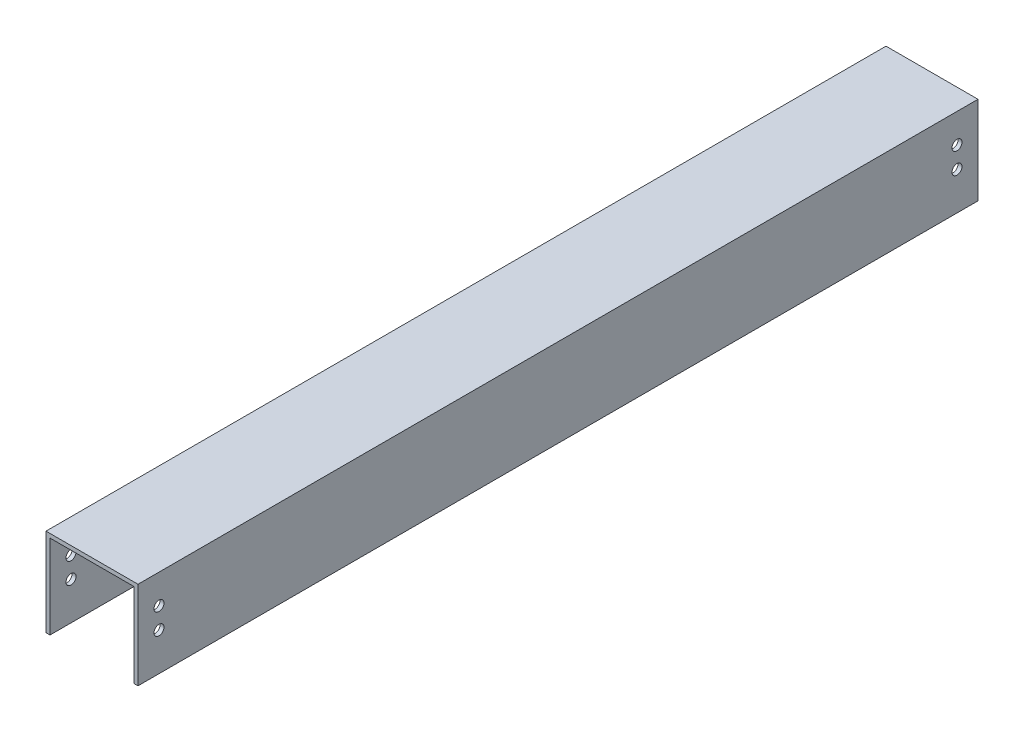
SolidWorks part; units mm, degrees
material "AISI 1020 Acero laminado en frío"
ref_plane "Alzado" through (0, 0, 0) normal (0, 0, 1) x (1, 0, 0)
ref_plane "Planta" through (0, 0, 0) normal (0, 1, 0) x (1, 0, 0)
ref_plane "Vista lateral" through (0, 0, 0) normal (1, 0, 0) x (0, 0, -1)
sketch "Croquis1" plane through (0, 0, 0) normal (0, 0, 1) x (1, 0, 0)
  line L0 (0, 0) -> (50, 0)
  line L1 (50, 0) -> (50, -100)
  line L2 (0, 0) -> (-50, 0)
  line L3 (-50, 0) -> (-50, -100)
  line L4 (0, 42.8285) -> (0, -43.566) construction
  line L5 (54.7625, 4.7625) -> (54.7625, -100)
  line L6 (0, 4.7625) -> (54.7625, 4.7625)
  line L7 (0, 4.7625) -> (-54.7625, 4.7625)
  line L8 (-54.7625, 4.7625) -> (-54.7625, -100)
  line L9 (50, -100) -> (54.7625, -100)
  line L10 (-50, -100) -> (-54.7625, -100)
  dimension "D1" = 100
  dimension "D2" = 100
  dimension "D3" = 100
  dimension "D4" = 4.7625
extrude "Saliente-Extruir1" add sketch "Croquis1" along normal mid plane 1000
hole_wizard "Taladro de margen para 7/161" positions "Croquis2" profile "Croquis3" hole size "7/16" standard "Ansi Inch"
sketch "Croquis2" plane through (-54.7625, -829.7412, 122.5883) normal (-1, 0, 0) x (0, 0, 1)
  point P0 (-597.5883, 774.7412)
  point P3 (-597.5883, 799.7412)
  point P6 (352.4117, 799.7412)
  point P9 (352.4117, 774.7412)
sketch "Croquis3" plane through (-54.7625, -55, -475) normal (0, 1, 0) x (0, 0, 1)
  line L0 (0, 0) -> (0, 155.0766)
  line L1 (0, 155.0766) -> (5.9525, 151.5)
  line L2 (5.9525, 151.5) -> (5.9525, 0)
  line L3 (5.9525, 0) -> (0, 0)
  line L4 (0, 155.0766) -> (-5.9525, 151.5) construction
  line L5 (0, -6.35) -> (0, 107.95) construction
  dimension "Diámetro de taladro" = 11.905
  dimension "Profundidad de taladro" = 151.5
  dimension "Ángulo de perforador" = 118
sketch "Croquis4" plane through (54.7625, 0, 0) normal (1, 0, 0) x (0, 0, -1)
  line L0 (0, 134.8922) -> (0, -149.1237) construction
  line L1 (0, -65) -> (-500, -65) construction
  line L4 (-500, -100) -> (500, -100) construction
  circle A0 centre (0, -65) radius 11.9063
  dimension "D1" = 23.8125
  dimension "D2" = 35
extrude "Saliente-Extruir2" add sketch "Croquis4" against normal through all
